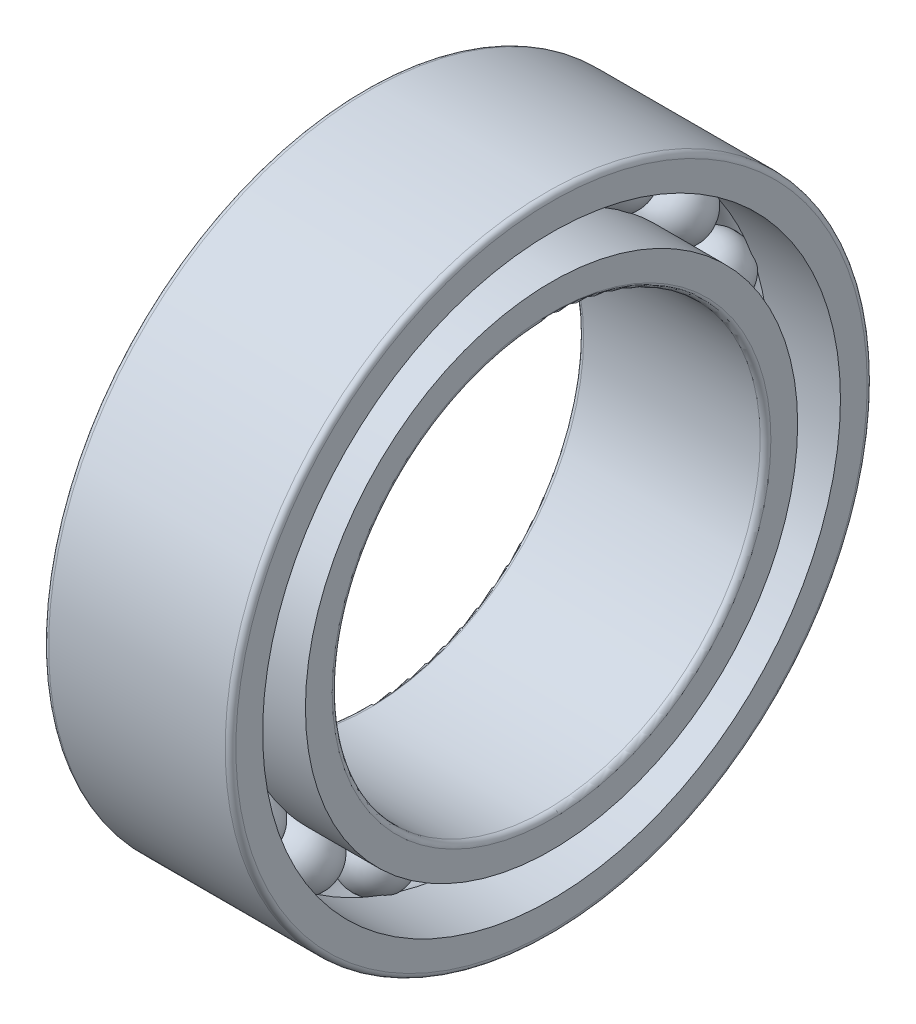
SolidWorks part; units mm, degrees
ref_plane "Plane1" through (0, 0, 0) normal (0, 0, 1) x (1, 0, 0)
ref_plane "Plane2" through (0, 0, 0) normal (0, 1, 0) x (1, 0, 0)
ref_plane "Plane3" through (0, 0, 0) normal (1, 0, 0) x (0, 0, -1)
other "Configuration Table"
sketch "Clipboard" plane through (0, 0, 0) normal (0, 0, 1) x (1, 0, 0)
  line L0 (-10, 0) -> (10, 0) construction
  line L1 (0, 0) -> (21.0122, -7.6478)
  line L2 (0, 0) -> (4.6985, 1.7101)
  line L3 (0, 0) -> (21.0122, -7.6478)
  line L4 (0, 0) -> (-22.3573, -0.3902)
  dimension "BallCLRad" = 5
  dimension "Count" = 20
sketch "CagSpiSke" plane through (0, 0, 0) normal (0, 0, 1) x (1, 0, 0)
  line L0 (0.06, 4.9) -> (0.06, 5.1)
  line L1 (0.06, 5.1) -> (-0.06, 5.1)
  line L2 (-0.06, 5.1) -> (-0.06, 4.9)
  line L3 (-0.06, 4.9) -> (0.06, 4.9)
  line L4 (-20.6375, 0) -> (20.6375, 0) construction
  line L5 (0, 0) -> (0, 23.7692) construction
  dimension "OD" = 10.2
  dimension "ID" = 9.8
revolve "CageSpine" add sketch "CagSpiSke" angle 0.001 about L4 reverse direction yes
ref_axis "Axis1" through (-50, 0, 0) along (1, 0, 0)
sketch "CagBalSke" plane through (0, 0, 0) normal (0, 0, 1) x (1, 0, 0)
  line L0 (-0.66, 5) -> (0.66, 5)
  line L1 (-1.905, 5) -> (1.905, 5) construction
  line L2 (-10, 0) -> (10, 0) construction
  line L3 (0, 0) -> (0, 24) construction
  arc A0 (0.66, 5) -> (-0.66, 5) centre (0, 5) cw
  dimension "BallCLRad" = 5
revolve "CageBall" [suppressed] add sketch "CagBalSke" angle 360 about L1 reverse direction yes
pattern_circular "CageBalls" [suppressed] count 20 every 18 about axis through (-50, 0, 0) along (1, 0, 0)
sketch "CagTrmODSke" plane through (0, 0, 0) normal (0, 0, 1) x (1, 0, 0)
  line L0 (0.661, 5.1) -> (0.661, 5.661)
  line L1 (0.661, 5.661) -> (-0.661, 5.661)
  line L2 (-0.661, 5.661) -> (-0.661, 5.1)
  line L3 (-0.661, 5.1) -> (0.661, 5.1)
  line L4 (-20.6375, 0) -> (20.6375, 0) construction
  line L5 (0, 0) -> (0, 25) construction
  dimension "Width" = 1.322
  dimension "ID" = 10.2
  dimension "OD" = 11.322
revolve "CageTrimOD" [suppressed] cut sketch "CagTrmODSke" angle 360 about L4 reverse direction yes
sketch "CagTrmIDSke" plane through (0, 0, 0) normal (0, 0, 1) x (1, 0, 0)
  line L0 (0.661, 4.341) -> (0.661, 4.9)
  line L1 (0.661, 4.9) -> (-0.661, 4.9)
  line L2 (-0.661, 4.9) -> (-0.661, 4.341)
  line L3 (-0.661, 4.341) -> (0.661, 4.341)
  line L4 (-20.6375, 0) -> (20.6375, 0) construction
  line L5 (0, 0) -> (0, 25) construction
  dimension "Width" = 1.322
  dimension "ID" = 8.682
  dimension "OD" = 9.8
revolve "CageTrimID" [suppressed] cut sketch "CagTrmIDSke" angle 360 about L4 reverse direction yes
sketch "BalSimSke" plane through (0, 0, 0) normal (0, 0, 1) x (1, 0, 0)
  line L0 (-10, 0) -> (10, 0) construction
  line L1 (-10, 5) -> (10, 5) construction
  line L2 (0, 0) -> (0, 23) construction
  circle A0 centre (0, 5) radius 0.6
  dimension "BallCLRad" = 5
revolve "BallsSimplified" [suppressed] add sketch "BalSimSke" angle 360 about L0
sketch "BalDetSke" plane through (0, 0, 0) normal (0, 0, 1) x (1, 0, 0)
  line L0 (-0.6, 5) -> (0.6, 5)
  line L1 (-1.905, 5) -> (1.905, 5) construction
  line L2 (0, 0) -> (0, 25) construction
  arc A0 (0.6, 5) -> (-0.6, 5) centre (0, 5) cw
  dimension "BallCLRad" = 5
revolve "BallDetailed" add sketch "BalDetSke" angle 360 about L1 reverse direction yes
sketch "InnRacSke" plane through (0, 0, 0) normal (0, 0, 1) x (1, 0, 0)
  line L0 (-0.4131, 4.6) -> (-1.75, 4.6)
  line L1 (-1.75, 4.6) -> (-1.75, 4.1)
  line L2 (-1.65, 4) -> (1.65, 4)
  line L3 (1.75, 4.1) -> (1.75, 4.6)
  line L4 (1.75, 4.6) -> (0.4131, 4.6)
  line L5 (-20.6375, 0) -> (20.6375, 0) construction
  line L6 (0, 0) -> (0, 30) construction
  arc A0 (-1.75, 4.1) -> (-1.65, 4) centre (-1.65, 4.1) ccw
  arc A1 (1.65, 4) -> (1.75, 4.1) centre (1.65, 4.1) ccw
  arc A2 (0.4131, 4.6) -> (-0.4131, 4.6) centre (0, 5) cw
  dimension "BallCLRad" = 5
  dimension "Fillet_radius" = 0.1
  dimension "Ball_diameter" = 1.15
  dimension "ID" = 8
  dimension "OD" = 9.2
  dimension "Width" = 3.5
revolve "InnerRace" add sketch "InnRacSke" angle 360 about L5 reverse direction yes
sketch "OutRacSke" plane through (0, 0, 0) normal (0, 0, 1) x (1, 0, 0)
  line L0 (-0.4131, 5.4) -> (-1.75, 5.4)
  line L1 (-1.75, 5.4) -> (-1.75, 5.9)
  line L2 (-1.65, 6) -> (1.65, 6)
  line L3 (1.75, 5.9) -> (1.75, 5.4)
  line L4 (1.75, 5.4) -> (0.4131, 5.4)
  line L5 (-20.6375, 0) -> (20.6375, 0) construction
  line L6 (0, 0) -> (0, 30) construction
  arc A0 (-1.75, 5.9) -> (-1.65, 6) centre (-1.65, 5.9) cw
  arc A1 (1.65, 6) -> (1.75, 5.9) centre (1.65, 5.9) cw
  arc A2 (0.4131, 5.4) -> (-0.4131, 5.4) centre (0, 5) ccw
  dimension "BallCLRad" = 5
  dimension "Fillet_radius" = 0.1
  dimension "Ball_diameter" = 1.15
  dimension "Width" = 3.5
revolve "OuterRace" add sketch "OutRacSke" angle 360 about L5 reverse direction yes
pattern_circular "BallsDetailed" count 20 every 18 about axis through (-50, 0, 0) along (1, 0, 0) of "BallDetailed"
equation "\"BallCLRad@Clipboard\" = ( \"OD@OutRacSke\" + \"ID@InnRacSke\" ) / 4"
equation "\"BallCLRad@BalSimSke\" = \"BallCLRad@Clipboard\""
equation "\"BallCLRad@BalDetSke\" = \"BallCLRad@Clipboard\""
equation "\"BallCLRad@InnRacSke\" = \"BallCLRad@Clipboard\""
equation "\"BallCLRad@OutRacSke\" = \"BallCLRad@Clipboard\""
equation "\"Ball_diameter@InnRacSke\" = \"Ball_diameter@BalDetSke\" - 0.05"
equation "\"Ball_diameter@OutRacSke\" = \"Ball_diameter@BalDetSke\" - 0.05"
equation "\"Ball_diameter@BalSimSke\" = \"Ball_diameter@BalDetSke\""
equation "\"Width@OutRacSke\" = \"Width@InnRacSke\""
equation "\"Fillet_radius@OutRacSke\" = \"Fillet_radius@InnRacSke\""
equation "\"Max_count@Clipboard\" = int( 3.14159265 / atn(( \"Ball_diameter@BalDetSke\" / 2) / sqr( \"BallCLRad@Clipboard\"  *  \"BallCLRad@Clipboard\" - ( \"Ball_diameter@BalDetSke\" / 2) *  ( \"Ball_diameter@BalDetSke\" / 2))))"
equation "\"Max_count@Clipboard\" = ((sgn( \"Max_count@Clipboard\" - \"Count@Clipboard\" )-1)*( \"Max_count@Clipboard\" - \"Count@Clipboard\" ))/-2+ \"Count@Clipboard\""
equation "\"Count@BallsDetailed\" = int( \"Show_count@Clipboard\" ) "
equation "\"Count@BallsDetailed\" = ((sgn( \"Count@BallsDetailed\" - \"Max_count@Clipboard\" )-1)*( \"Count@BallsDetailed\" - \"Max_count@Clipboard\" ))/-2+ \"Max_count@Clipboard\""
equation "\"Count@BallsDetailed\" = ((sgn( \"Count@BallsDetailed\" - \"Min_count@Clipboard\" )+1)*( \"Count@BallsDetailed\" - \"Min_count@Clipboard\"))/2 +\"Min_count@Clipboard\""
equation "\"Angle@BallsDetailed\" = 360.0 / \"Max_count@Clipboard\""
equation "\"BallCLRad@CagBalSke\" = \"BallCLRad@Clipboard\""
equation "\"Count@CageBalls\" = \"Count@BallsDetailed\""
equation "\"Angle@CageBalls\" = \"Angle@BallsDetailed\""
equation "\"Angle@CageSpine\" =  \"Angle@CageBalls\" * ( \"Count@CageBalls\" -1 + int( \"Count@CageBalls\" / \"Max_count@Clipboard\" ) )  + 0.001 -  int( \"Count@CageBalls\" / \"Max_count@Clipboard\" ) * 0.001"
equation "\"Angle@CageSpine\" =  \"Angle@CageSpine\" * int( \"Min_count@Clipboard\" / 2) + int(1 / \"Min_count@Clipboard\")  * 0.001"
equation "\"CageWallOD@CagBalSke\" =  \"Ball_diameter@BalDetSke\" * 1.1"
equation "\"Thickness@CagSpiSke\" =  \"Ball_diameter@BalDetSke\" * 0.1"
equation "\"OD@CagTrmODSke\" = \"BallCLRad@Clipboard\" * 2 + \"CageWallOD@CagBalSke\" + 0.002"
equation "\"ID@CagTrmODSke\" = \"BallCLRad@Clipboard\" * 2 + \"Ball_diameter@BalDetSke\" / 6"
equation "\"OD@CagTrmIDSke\" = \"BallCLRad@Clipboard\" * 2 - \"Ball_diameter@BalDetSke\" / 6"
equation "\"ID@CagTrmIDSke\" = \"BallCLRad@Clipboard\" * 2 - \"CageWallOD@CagBalSke\" + 0.002"
equation "\"OD@CagSpiSke\" = \"ID@CagTrmODSke\""
equation "\"ID@CagSpiSke\" = \"OD@CagTrmIDSke\""
equation "\"Width@CagTrmODSke\" = \"CageWallOD@CagBalSke\" + 0.002"
equation "\"Width@CagTrmIDSke\" = \"CageWallOD@CagBalSke\" + 0.002"
